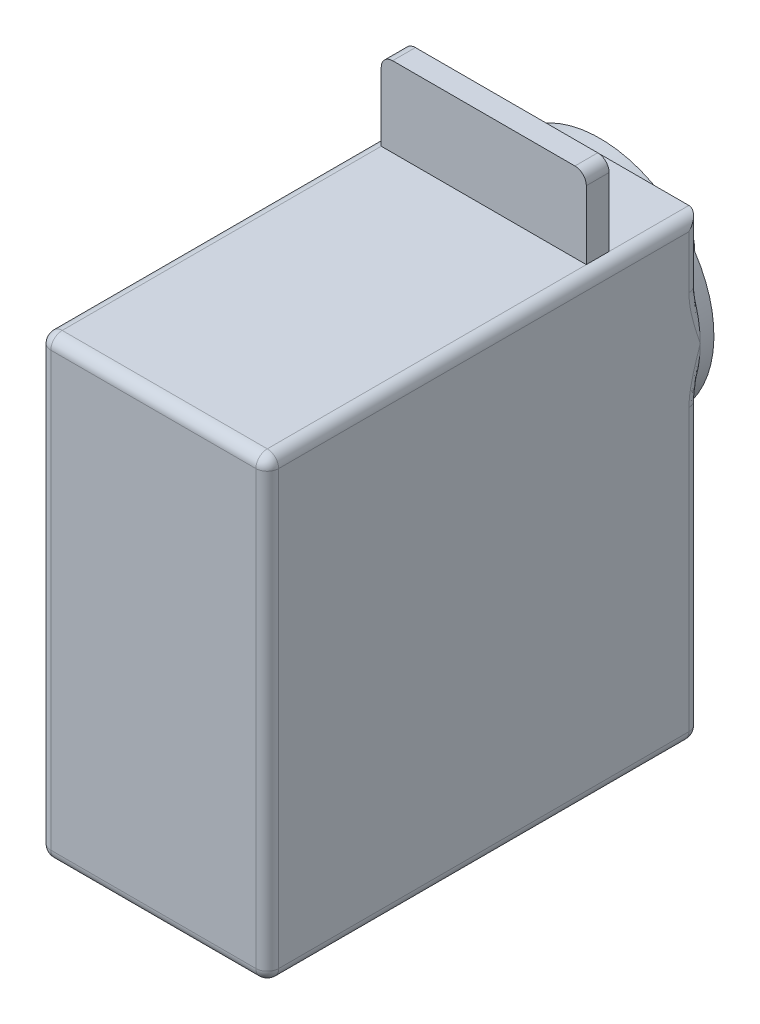
SolidWorks part; units mm, degrees
ref_plane "정면" through (0, 0, 0) normal (0, 0, 1) x (1, 0, 0)
ref_plane "윗면" through (0, 0, 0) normal (0, 1, 0) x (1, 0, 0)
ref_plane "우측면" through (0, 0, 0) normal (1, 0, 0) x (0, 0, -1)
sketch "스케치1" plane through (0, 0, 0) normal (0, 0, 1) x (1, 0, 0)
  line L1 (-10, -20) -> (10, -20)
  line L2 (-10, -20) -> (-10, 20)
  line L3 (-10, 20) -> (10, 20)
  line L4 (10, -20) -> (10, 20)
  line L5 (-10, -20) -> (10, 20) construction
  line L6 (-10, 20) -> (10, -20) construction
  point P0 (0, 0)
  dimension "D1" = 20
  dimension "D2" = 40
extrude "보스-돌출1" add sketch "스케치1" along normal blind 40
sketch "스케치2" plane through (0, 0, 0) normal (0, 0, 1) x (1, 0, 0)
  line L0 (0, 20) -> (0, 0) construction
  line L1 (10, 20) -> (-10, 20) construction
  line L6 (8, 4) -> (8, -12)
  line L7 (8, -12) -> (-8, -12)
  line L8 (0, 0) -> (0, -12) construction
  line L9 (0, 0) -> (0, -18.9263) construction
  line L10 (10, -20) -> (10, 20)
  line L11 (-10, -20) -> (10, -20)
  line L12 (-10, 20) -> (-10, -20)
  line L13 (10, 20) -> (-10, 20)
  line L14 (10, -20) -> (10, 20)
  line L15 (-10, -20) -> (10, -20)
  line L16 (-10, 20) -> (-10, -20)
  line L17 (10, 20) -> (-10, 20)
  line L18 (-8, 4) -> (-8, -12)
  circle A0 centre (0, 10) radius 2.5
  circle A1 centre (0, 10) radius 10
  circle A2 centre (0, -8.5) radius 5
  circle A3 centre (0, 10) radius 6
  dimension "D2" = 5
  dimension "D6" = 10
  dimension "D8" = 12
  dimension "D1" = 10
  dimension "D4" = 16
  dimension "D5" = 8
  dimension "D7" = 3.5
  dimension "D3" = 0
extrude "컷-돌출3" cut sketch "스케치2" along normal blind 2 contours A2 L7 L18 A1 L16 L15 L14 L6 | A1 L14 L17 | A1 L17 L16 region at (9.8289, 6.7237, 0) region at (7.7663, 17.7663, 0) region at (-7.7663, 17.7663, 0)
extrude "컷-돌출4" cut sketch "스케치2<4>" along normal blind 1.2 contours L7 A2 region at (0, -12.6085, 0)
sketch "스케치2<4>" plane through (0, 0, 0) normal (0, 0, 1) x (1, 0, 0) same geometry as "스케치2"
extrude "컷-돌출5" cut sketch "스케치2<5>" along normal blind 0.8 contours A1 A3 | A2 L7 L6 A1 L18 | L7 A2 region at (7.7737, -4, 0) region at (0, 0.2828, 0) region at (0, -8.0734, 0)
sketch "스케치2<5>" plane through (0, 0, 0) normal (0, 0, 1) x (1, 0, 0) same geometry as "스케치2"
extrude "보스-돌출2" add sketch "스케치2<6>" against normal blind 5 contours A0 region at (0, 10, 0)
sketch "스케치2<6>" plane through (0, 0, 0) normal (0, 0, 1) x (1, 0, 0) same geometry as "스케치2"
fillet "필렛1" radius 1 13 edges at (-10, -5, 2) (10, 15, 2) (0, -20, 40) (-10, 0, 40) (0, 20, 40) (10, 0, 40) (-10, -20, 21) (10, -20, 21) (0, -20, 2) (-10, 15, 2) (10, -5, 2) (-10, 20, 21) (10, 20, 21)
sketch "스케치3" plane through (0, 20, 0) normal (0, 1, 0) x (1, 0, 0)
  line L5 (0, -2) -> (-9, -2)
  line L6 (-9, -2) -> (-9, -39)
  line L7 (-9, -39) -> (9, -39)
  line L8 (9, -39) -> (9, -2)
  line L9 (9, -2) -> (0, -2)
  line L10 (0, -2) -> (-9, -2)
  line L11 (-9, -2) -> (-9, -39)
  line L12 (-9, -39) -> (9, -39)
  line L13 (9, -39) -> (9, -2)
  line L14 (9, -2) -> (0, -2)
  line L21 (9, -9) -> (-9, -9)
  line L22 (-9, -11) -> (9, -11)
  dimension "D2" = 7
  dimension "D3" = 2
  dimension "D1" = 0
extrude "보스-돌출3" add sketch "스케치3" along normal blind 7 contours L11 L22 L13 L21 region at (0, 20, 10)
fillet "필렛2" radius 1 2 edges at (-9, 27, 10) (9, 27, 10)
